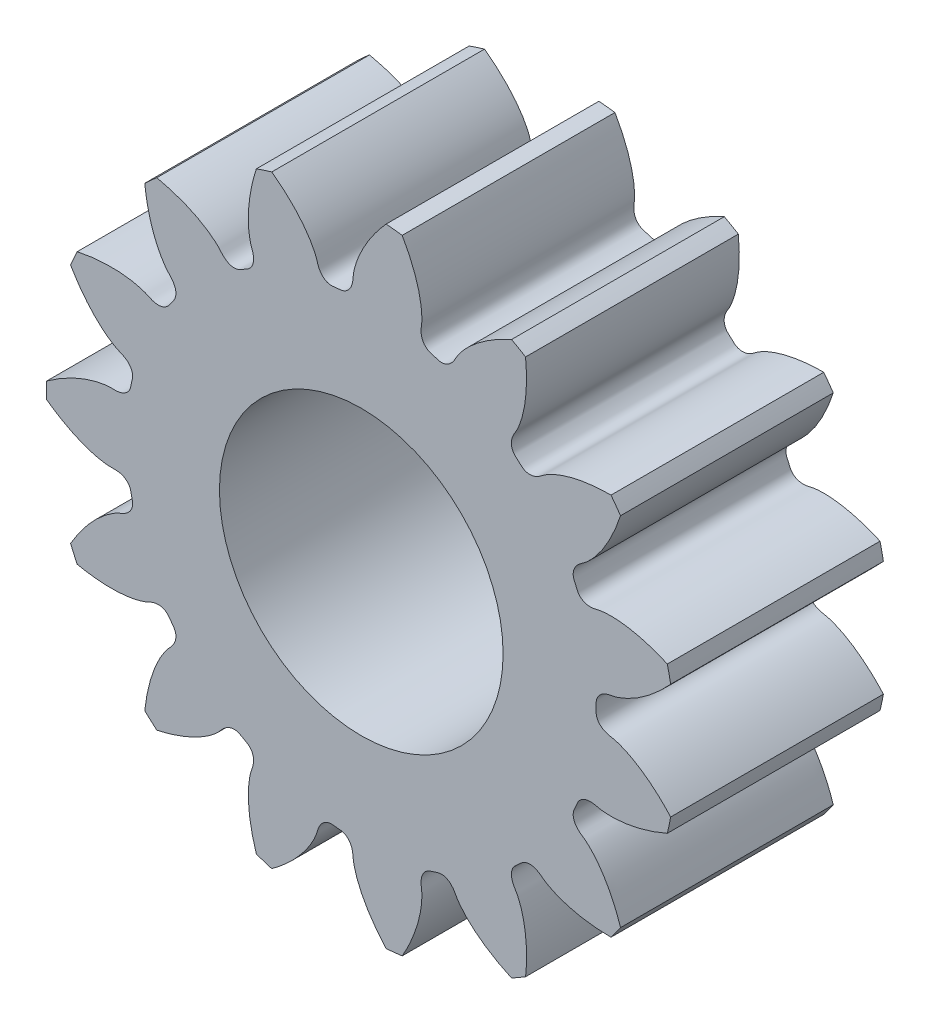
SolidWorks part; units mm, degrees
material "Д16 ГОСТ 4784-97"
ref_plane "FRONT" through (0, 0, 0) normal (0, 0, 1) x (1, 0, 0)
ref_plane "TOP" through (0, 0, 0) normal (0, 1, 0) x (1, 0, 0)
ref_plane "RIGHT" through (0, 0, 0) normal (1, 0, 0) x (0, 0, -1)
ref_axis "Ось1" through (0, 0, 50) along (0, 0, -1)
sketch "SketchRevolveSpurAssembly02Pinion" plane through (0, 0, 0) normal (1, 0, 0) x (0, 0, -1)
  line L0 (0, 0) -> (1, 0) construction
  line L1 (-9.525, 0) -> (-9.525, 8.875)
  line L2 (-9.525, 8.875) -> (-3.525, 8.875)
  line L3 (-3.525, 8.875) -> (-3.525, 0)
  line L4 (-3.525, 0) -> (-9.525, 0)
  dimension "D1" = 6
revolve "SpurAssembly02Pinion" add sketch "SketchRevolveSpurAssembly02Pinion" angle 360 about L0
sketch "SketchToothSpurAssembly02Pinion" plane through (0, 0, 0) normal (0, 0, 1) x (1, 0, 0)
  arc A0 (8.7833, 1.6863) -> (8.7833, -1.6863) centre (0, 0) cw
  spline S0 degree 3 poles (8.7833, -1.6863) (8.6937, -1.5837) (8.5573, -1.4387) (8.3694, -1.2616) (8.2356, -1.145) (8.1057, -1.0404) (7.9804, -0.9474) (7.8606, -0.8655) (7.7467, -0.794) (7.6394, -0.7323) (7.5394, -0.6799) (7.4471, -0.636) (7.363, -0.6) (7.2877, -0.5711) (7.2215, -0.5486) (7.1647, -0.5319) (7.0913, -0.5128) (7.0287, -0.5043) (6.9767, -0.4919) (6.9572, -0.4868) (6.9379, -0.4811) (6.9188, -0.4749) (6.8997, -0.468) (6.8808, -0.4605) (6.8619, -0.4522) (6.843, -0.443) (6.8239, -0.4328) (6.8048, -0.4214) (6.7856, -0.4086) (6.7662, -0.3941) (6.7467, -0.3778) (6.7271, -0.3592) (6.7078, -0.3379) (6.689, -0.3136) (6.6712, -0.2861) (6.655, -0.255) (6.6413, -0.2204) (6.631, -0.1827) (6.6251, -0.1442) (6.6232, -0.083) (6.6263, 0) (6.6232, 0.083) (6.6251, 0.1442) (6.631, 0.1827) (6.6413, 0.2204) (6.655, 0.255) (6.6712, 0.2861) (6.689, 0.3136) (6.7078, 0.3379) (6.7271, 0.3592) (6.7467, 0.3778) (6.7662, 0.3941) (6.7856, 0.4086) (6.8048, 0.4214) (6.8239, 0.4328) (6.843, 0.443) (6.8619, 0.4522) (6.8808, 0.4605) (6.8997, 0.468) (6.9188, 0.4749) (6.9379, 0.4811) (6.9572, 0.4868) (6.9767, 0.4919) (7.0287, 0.5043) (7.0913, 0.5128) (7.1647, 0.5319) (7.2215, 0.5486) (7.2877, 0.5711) (7.363, 0.6) (7.4471, 0.636) (7.5394, 0.6799) (7.6394, 0.7323) (7.7467, 0.794) (7.8606, 0.8655) (7.9804, 0.9474) (8.1057, 1.0404) (8.2356, 1.145) (8.3694, 1.2616) (8.5573, 1.4387) (8.6937, 1.5837) (8.7833, 1.6863) knots 0 0 0 0 0.071008 0.103709 0.134542 0.163506 0.190601 0.215828 0.239186 0.260675 0.280296 0.298048 0.313931 0.327946 0.340092 0.35037 0.358779 0.37965 0.383168 0.386667 0.390156 0.393647 0.397153 0.400689 0.404271 0.40792 0.411659 0.415515 0.419519 0.423705 0.428112 0.432781 0.437755 0.443073 0.448767 0.454851 0.461317 0.468122 0.475185 0.481526 0.5 0.518474 0.524815 0.531878 0.538683 0.545149 0.551233 0.556927 0.562245 0.567219 0.571888 0.576295 0.580481 0.584485 0.588341 0.59208 0.595729 0.599311 0.602847 0.606353 0.609844 0.613333 0.616832 0.62035 0.641221 0.64963 0.659908 0.672054 0.686069 0.701952 0.719704 0.739325 0.760814 0.784172 0.809399 0.836494 0.865458 0.896291 0.928992 1 1 1 1
extrude "ToothExtrudeCutSpurAssembly02Pinion" cut sketch "SketchToothSpurAssembly02Pinion" against normal blind 9.525 and the other way blind 9.525
pattern_circular "PatternSpurAssembly02Pinion" count 15 every 24 about axis through (0, 0, 50) along (0, 0, -1) of "ToothExtrudeCutSpurAssembly02Pinion"
sketch "Эскиз5" plane through (0, 0, 9.525) normal (0, 0, 1) x (1, 0, 0)
  circle A0 centre (0, 0) radius 4
extrude "Вырез-Вытянуть2" cut sketch "Эскиз5" against normal through all and the other way through all
sketch "AuxiliarySketchSpurAssembly02Pinion" plane through (0, 0, 0) normal (0, 0, 1) x (1, 0, 0)
  circle A0 centre (0, 0) radius 7.5 construction
  circle A1 centre (0, 0) radius 7.0477 construction
  circle A2 centre (0, 0) radius 7.0718 construction
  circle A3 centre (0, 0) radius 8.875 construction
  circle A4 centre (0, 0) radius 6.625 construction
  dimension "PitchDiameter" = 15
  dimension "BaseDiameter" = 14.0954
  dimension "FormDiameter" = 14.1437
  dimension "MajorDiameter" = 17.75
  dimension "MinorDiameter" = 13.25
